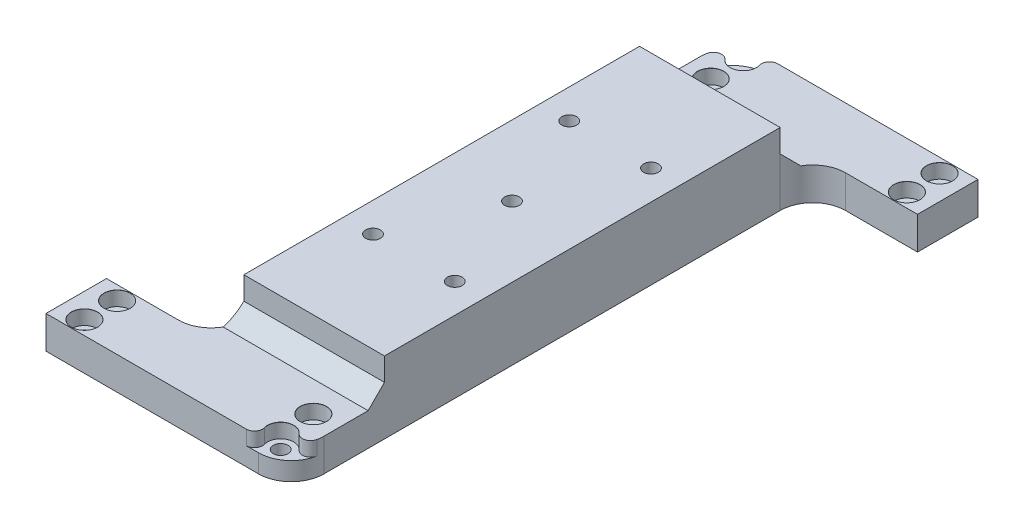
SolidWorks part; units mm, degrees
material "7075-T6 (SN)"
ref_plane "Front Plane" through (0, 0, 0) normal (0, 0, 1) x (1, 0, 0)
ref_plane "Top Plane" through (0, 0, 0) normal (0, 1, 0) x (1, 0, 0)
ref_plane "Right Plane" through (0, 0, 0) normal (1, 0, 0) x (0, 0, -1)
sketch "Sketch1" plane through (0, 0, 0) normal (0, 1, 0) x (1, 0, 0)
  line L0 (0, 0) -> (-21.5, 0) construction
  line L1 (-21.5, -89) -> (21.5, -89)
  line L2 (-21.5, -70.5) -> (-21.5, 89)
  line L5 (-21.5, -89) -> (21.5, 89) construction
  line L6 (-21.5, 89) -> (21.5, -89) construction
  line L7 (-53.5, -89) -> (-21.5, -89)
  line L8 (-53.5, -89) -> (-53.5, -70.5)
  line L9 (-53.5, -70.5) -> (-21.5, -70.5)
  line L11 (0, 0) -> (0, 89) construction
  line L12 (21.5, 70.5) -> (21.5, -89)
  line L13 (-21.5, 89) -> (53.5, 89)
  line L16 (53.5, 89) -> (53.5, 70.5)
  line L17 (53.5, 70.5) -> (21.5, 70.5)
  point P0 (0, 0)
  dimension "D1" = 18.5
  dimension "D2" = 43
  dimension "D3" = 32
  dimension "D4" = 32
  dimension "D5" = 18.5
extrude "Boss-Extrude1" add sketch "Sketch1" along normal blind 10
fillet "Fillet1" radius 10 4 edges at (-21.5, 5, -89) (21.5, 5, 89) (21.5, 5, -70.5) (-21.5, 5, 70.5)
sketch "Sketch2" plane through (0, 10, 0) normal (0, 1, 0) x (1, 0, 0)
  circle A0 centre (-14, 74.75) radius 1.75
  circle A1 centre (-14, 84.75) radius 1.75
  circle A2 centre (46, 74.75) radius 1.75
  circle A3 centre (46, 84.75) radius 1.75
  circle A4 centre (-46, -74.75) radius 1.75
  circle A5 centre (-46, -84.75) radius 1.75
  circle A6 centre (14, -74.75) radius 1.75
  circle A7 centre (14, -84.75) radius 1.75
extrude "Cut-Extrude1" cut sketch "Sketch2" against normal blind 10
hole_wizard "CBORE for M4 Hex Socket Head Cap Screw1" positions "Sketch3" profile "Sketch4" counterbore size "M4" standard "DIN"
sketch "Sketch3" plane through (0, 10, 0) normal (0, 1, 0) x (1, 0, 0)
  point P0 (-14, 74.75)
  point P3 (-14, 84.75)
  point P10 (46, 74.75)
  point P13 (14, -74.75)
  point P16 (14, -84.75)
  point P19 (-46, -84.75)
  point P22 (-46, -74.75)
  point P25 (46, 84.75)
sketch "Sketch4" plane through (-14, 10, -74.75) normal (1, 0, 0) x (0, 0, 1)
  line L0 (0, 0) -> (0, 11.3519)
  line L1 (0, 11.3519) -> (2.25, 10)
  line L2 (2.25, 10) -> (2.25, 4.4)
  line L3 (2.25, 4.4) -> (4, 4.4)
  line L5 (4, 4.4) -> (4, 0.025)
  line L6 (4, 0.025) -> (4.025, 0)
  line L7 (4.025, 0) -> (0, 0)
  line L8 (-4, 0.025) -> (-4.025, 0) construction
  line L10 (0, 11.3519) -> (-2.25, 10) construction
  line L11 (0, -6.35) -> (0, 107.95) construction
  dimension "Hole Dia." = 4.5
  dimension "Hole Depth" = 10
  dimension "C'Bore Dia." = 8
  dimension "C'Bore Depth" = 4.4
  dimension "Near C'Sink Dia." = 8.05
  dimension "Near C'Sink Angle" = 90
  dimension "Drill Angle" = 118
fillet "Fillet2" radius 2.5 2 edges at (-17.087, 7.7875, -87.2937) (-13.7548, 7.7875, -88.7425)
fillet "Fillet3" radius 2.5 2 edges at (13.7548, 7.7875, 88.7425) (17.087, 7.7875, 87.2937)
sketch "Sketch5" plane through (0, 10, 0) normal (0, 1, 0) x (1, 0, 0)
  line L1 (21.5, 60.5) -> (-21.5, 60.5)
  line L2 (21.5, 60.5) -> (21.5, -60.5)
  line L3 (21.5, -60.5) -> (-21.5, -60.5)
  line L4 (-21.5, 60.5) -> (-21.5, -60.5)
extrude "Boss-Extrude2" add sketch "Sketch5" along normal blind 12
chamfer "Chamfer1" distance 5 angle 45 2 edges at (0, 10, -60.5) (0, 10, 60.5)
sketch "Sketch7" plane through (0, 22, 0) normal (0, 1, 0) x (1, 0, 0)
  circle A0 centre (0, 0) radius 2.25
  dimension "D1" = 4.5
extrude "Cut-Extrude2" cut sketch "Sketch7" against normal blind 10
sketch "Sketch8" plane through (0, 22, 0) normal (0, 1, 0) x (1, 0, 0)
  circle A0 centre (12.5, 30) radius 2.25
  circle A1 centre (-12.5, 30) radius 2.25
  circle A2 centre (-12.5, -30) radius 2.25
  circle A3 centre (12.5, -30) radius 2.25
  dimension "D1" = 4.5
extrude "Cut-Extrude3" cut sketch "Sketch8" against normal blind 10
